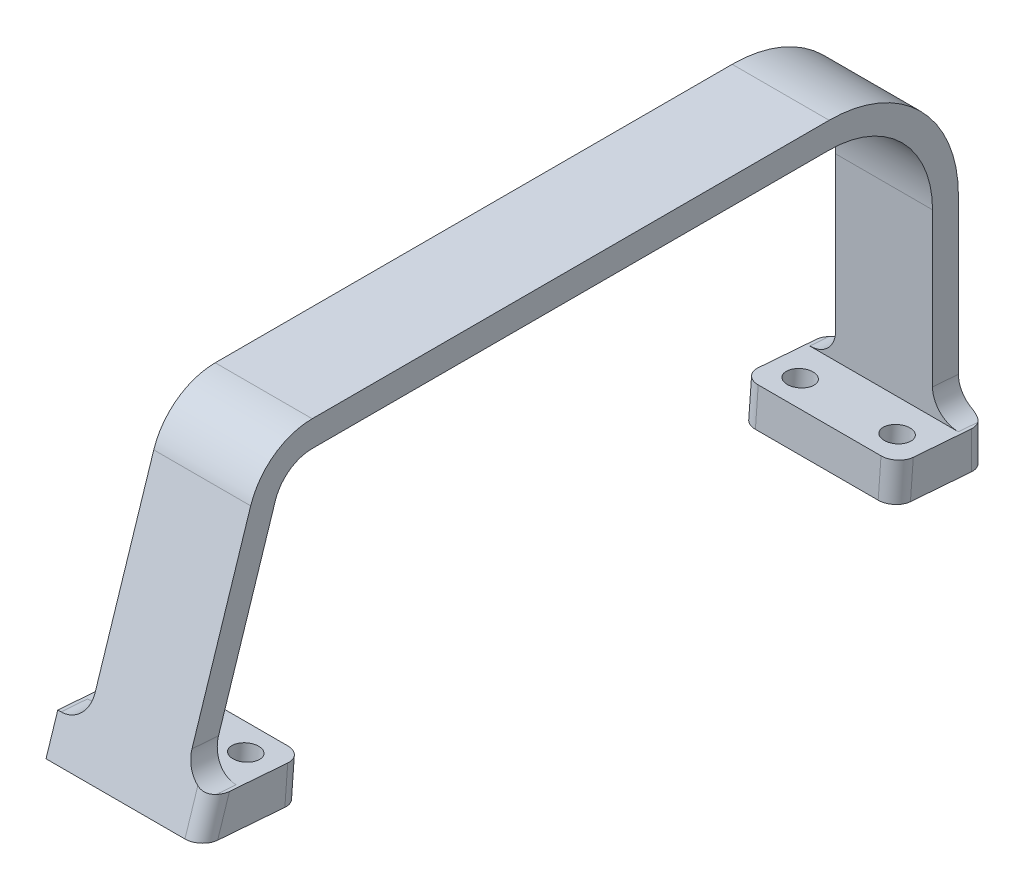
SolidWorks part; units mm, degrees
note: The reader was unsure of these and kept them because the rebuilt part matched: shared geometry of "Sketch1<4>".
ref_plane "Front Plane" through (0, 0, 0) normal (0, 0, 1) x (1, 0, 0)
ref_plane "Top Plane" through (0, 0, 0) normal (0, 1, 0) x (1, 0, 0)
ref_plane "Right Plane" through (0, 0, 0) normal (1, 0, 0) x (0, 0, -1)
sketch "Sketch1" plane through (249.7714, 90.1979, 68.8584) normal (1, 0, 0) x (0, 0, -1)
  line L0 (280.4073, 20.9839) -> (280.4073, 54.8059)
  line L1 (260.4073, 74.8059) -> (180.4073, 74.8059)
  line L2 (170.8946, 67.8894) -> (158.7192, 30.3282)
  line L3 (276.4073, 21.2911) -> (276.4073, 54.8059)
  line L4 (118.8342, -21.0437) -> (146.5698, -21.0437) construction
  line L5 (137.5507, -68.5354) -> (136.2221, -67.0405) construction
  line L6 (236.0263, -68.5354) -> (234.6977, -67.0405) construction
  line L7 (115.1532, -78.1941) -> (341.6973, -78.1941) construction
  line L8 (174.6997, 66.656) -> (162.5243, 29.0948) construction
  line L9 (260.4073, 70.8059) -> (180.4073, 70.8059)
  line L10 (174.6997, 66.656) -> (162.822, 30.0132)
  line L11 (280.4073, 20.9839) -> (276.4073, 21.2911)
  line L12 (143.7192, 33.2418) -> (143.7192, 31.4801) construction
  line L13 (254.1601, 22.9994) -> (289.0573, 20.3197) construction
  line L15 (276.4073, 20.9839) -> (276.4073, 54.8059) construction
  line L16 (158.7192, 30.3282) -> (162.822, 30.0132)
  line L18 (162.822, 30.0132) -> (174.1763, 29.1413)
  line L19 (174.1763, 29.1413) -> (174.6166, 34.8744)
  line L20 (276.4073, 17.2563) -> (276.4073, 18.2823) construction
  line L21 (276.4073, 17.2563) -> (276.4073, 18.2823) construction
  line L22 (174.6166, 34.8744) -> (164.6459, 35.6401)
  line L23 (276.4073, 21.2911) -> (265.9965, 22.0905)
  line L24 (265.9965, 22.0905) -> (266.4367, 27.8237)
  line L25 (266.4367, 27.8237) -> (276.4073, 27.058)
  line L26 (164.6459, 35.6401) -> (160.5431, 35.9551)
  line L27 (276.4073, 27.058) -> (280.4073, 26.7509)
  line L32 (120.0573, 33.297) -> (289.0573, 20.3197) construction
  circle A0 centre (160.0573, -47.1941) radius 31 construction
  circle A1 centre (258.533, -47.1941) radius 31 construction
  arc A2 (280.4073, 54.8059) -> (260.4073, 74.8059) centre (260.4073, 54.8059) ccw
  arc A3 (180.4073, 74.8059) -> (170.8946, 67.8894) centre (180.4073, 64.8059) ccw
  arc A4 (276.4073, 54.8059) -> (260.4073, 70.8059) centre (260.4073, 54.8059) ccw
  arc A5 (180.4073, 70.8059) -> (174.6997, 66.656) centre (180.4073, 64.8059) ccw
  dimension "D1" = 20
  dimension "D2" = 10
  dimension "D3" = 4
  dimension "D4" = 153
  dimension "D5" = 15
  dimension "D6" = 80
  dimension "D7" = 5.75
  dimension "D8" = 10
extrude "Boss-Extrude1" add sketch "Sketch1" along normal mid plane 15
extrude "Boss-Extrude3" add sketch "Sketch1<4>" along normal mid plane 24 contours L19 L22 L10 L18 | L10 L26 L2 L16 | L27 L3 L11 L0 | L25 L24 L23 L3
sketch "Sketch1<4>" plane through (249.7714, 90.1979, 68.8584) normal (1, 0, 0) x (0, 0, -1) same geometry as "Sketch1"
fillet "Fillet1" radius 2.5 7 edges at (261.7714, 114.0653, -211.549) (237.7714, 114.0653, -211.549) (237.7714, 115.155, -197.3582) (261.7714, 115.155, -197.3582) (237.7714, 122.2058, -105.5381) (261.7714, 122.2058, -105.5381) (261.7714, 123.3396, -90.7728)
fillet "Fillet2" radius 4 4 edges at (257.2714, 125.9955, -93.7361) (242.2714, 125.9955, -93.7361) (242.2714, 117.1024, -209.549) (257.2714, 117.1024, -209.549)
sketch "Sketch5" plane through (0, 132.4126, -10.1678) normal (0, 0.9971, -0.0766) x (1, 0, 0)
  line L0 (249.7714, 197.9622) -> (249.7714, 85.8718) construction
  line L1 (261.2714, 197.9622) -> (238.2714, 197.9622) construction
  line L2 (261.2714, 85.8718) -> (238.2714, 85.8718) construction
  line L3 (185.9689, 141.917) -> (203.1825, 141.917) construction
  line L4 (259.2714, 187.9622) -> (240.2714, 187.9622) construction
  line L5 (237.7714, 190.4622) -> (237.7714, 199.4666) construction
  circle A0 centre (242.2714, 192.4622) radius 2
  circle A1 centre (257.2714, 192.4622) radius 2
  circle A2 centre (242.2714, 91.3718) radius 2
  circle A3 centre (257.2714, 91.3718) radius 2
  point P9 (249.7714, 141.917)
  dimension "D1" = 4
  dimension "D3" = 4.5
  dimension "D4" = 15
  dimension "D2" = 4.5
extrude "Cut-Extrude1" cut sketch "Sketch5" against normal up to next
